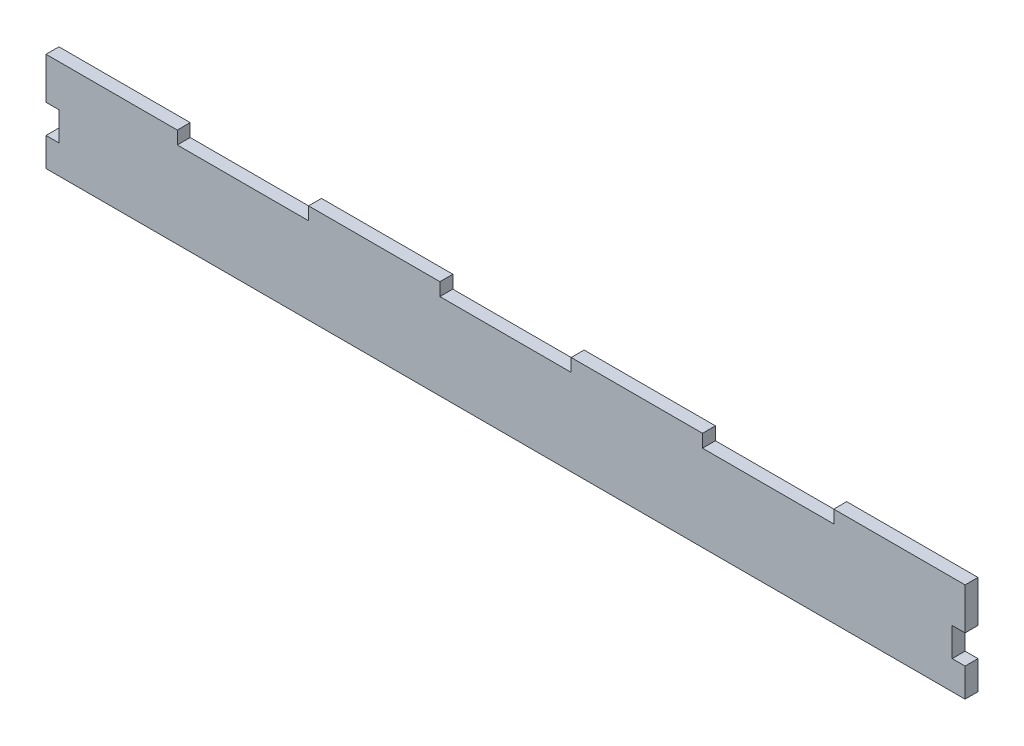
SolidWorks part; units mm, degrees
ref_plane "Front Plane" through (0, 0, 0) normal (0, 0, 1) x (1, 0, 0)
ref_plane "Top Plane" through (0, 0, 0) normal (0, 1, 0) x (1, 0, 0)
ref_plane "Right Plane" through (0, 0, 0) normal (1, 0, 0) x (0, 0, -1)
sketch "Sketch1" plane through (0, 0, 0) normal (0, 1, 0) x (1, 0, 0)
  line L1 (-207.5, -63.25) -> (207.5, -63.25)
  line L2 (-207.5, -63.25) -> (-207.5, 63.25)
  line L3 (-207.5, 63.25) -> (207.5, 63.25)
  line L4 (207.5, -63.25) -> (207.5, 63.25)
  line L5 (-207.5, -63.25) -> (207.5, 63.25) construction
  line L6 (-207.5, 63.25) -> (207.5, -63.25) construction
  point P0 (0, 0)
  dimension "D1" = 126.5
  dimension "D2" = 415
extrude "Boss-Extrude1" add sketch "Sketch1" along normal blind 6
sketch "Sketch2" plane through (0, 6, 0) normal (0, 1, 0) x (1, 0, 0)
  line L0 (213.5, -69.25) -> (213.5, 69.25)
  line L3 (-213.5, -69.25) -> (213.5, -69.25)
  line L4 (207.5, -63.25) -> (207.5, 63.25)
  line L5 (207.5, 63.25) -> (-207.5, 63.25)
  line L6 (-207.5, 63.25) -> (-207.5, -63.25)
  line L7 (-207.5, -63.25) -> (207.5, -63.25)
  line L8 (207.5, -63.25) -> (207.5, 63.25)
  line L9 (207.5, 63.25) -> (-207.5, 63.25)
  line L10 (-207.5, 63.25) -> (-207.5, -63.25)
  line L11 (-207.5, -63.25) -> (207.5, -63.25)
  line L12 (231.5, -87.25) -> (231.5, 87.25)
  line L13 (231.5, 87.25) -> (-231.5, 87.25)
  line L14 (-231.5, 87.25) -> (-231.5, -87.25)
  line L15 (-231.5, -87.25) -> (231.5, -87.25)
  line L16 (237.5, -93.25) -> (237.5, 93.25)
  line L19 (-237.5, -93.25) -> (237.5, -93.25)
  line L20 (213.5, 69.25) -> (-213.5, 69.25) construction
  line L21 (-213.5, 69.25) -> (-213.5, -69.25) construction
  line L22 (-213.5, -69.25) -> (-213.5, -63.25)
  line L27 (152.5, 69.25) -> (91.5, 69.25)
  line L28 (152.5, 69.25) -> (152.5, 63.25)
  line L29 (152.5, 63.25) -> (91.5, 63.25)
  line L30 (91.5, 69.25) -> (91.5, 63.25)
  line L31 (91.5, 69.25) -> (30.5, 69.25)
  line L32 (91.5, 69.25) -> (91.5, 63.25)
  line L33 (91.5, 63.25) -> (30.5, 63.25)
  line L34 (30.5, 69.25) -> (30.5, 63.25)
  line L35 (30.5, 69.25) -> (-30.5, 69.25)
  line L36 (30.5, 69.25) -> (30.5, 63.25)
  line L37 (30.5, 63.25) -> (-30.5, 63.25)
  line L38 (-30.5, 69.25) -> (-30.5, 63.25)
  line L39 (-30.5, 69.25) -> (-91.5, 69.25)
  line L40 (-30.5, 69.25) -> (-30.5, 63.25)
  line L41 (-30.5, 63.25) -> (-91.5, 63.25)
  line L42 (-91.5, 69.25) -> (-91.5, 63.25)
  line L43 (-91.5, 69.25) -> (-152.5, 69.25)
  line L44 (-91.5, 69.25) -> (-91.5, 63.25)
  line L45 (-91.5, 63.25) -> (-152.5, 63.25)
  line L46 (-152.5, 69.25) -> (-152.5, 63.25)
  line L47 (-152.5, 69.25) -> (-213.5, 69.25)
  line L48 (-152.5, 69.25) -> (-152.5, 63.25)
  line L49 (-152.5, 63.25) -> (-213.5, 63.25)
  line L50 (-213.5, 69.25) -> (-213.5, 63.25)
  line L51 (-213.5, 63.25) -> (-207.5, 63.25)
  line L52 (-213.5, 63.25) -> (-213.5, 37.95)
  line L53 (-213.5, 37.95) -> (-207.5, 37.95)
  line L54 (-207.5, 63.25) -> (-207.5, 37.95)
  line L55 (-207.5, 37.95) -> (-213.5, 37.95)
  line L56 (-207.5, 37.95) -> (-207.5, 12.65)
  line L57 (-207.5, 12.65) -> (-213.5, 12.65)
  line L58 (-213.5, 37.95) -> (-213.5, 12.65)
  line L59 (-213.5, 12.65) -> (-207.5, 12.65)
  line L60 (-213.5, 12.65) -> (-213.5, -12.65)
  line L61 (-213.5, -12.65) -> (-207.5, -12.65)
  line L62 (-207.5, 12.65) -> (-207.5, -12.65)
  line L63 (-207.5, -12.65) -> (-213.5, -12.65)
  line L64 (-207.5, -12.65) -> (-207.5, -37.95)
  line L65 (-207.5, -37.95) -> (-213.5, -37.95)
  line L66 (-213.5, -12.65) -> (-213.5, -37.95)
  line L67 (-213.5, -37.95) -> (-207.5, -37.95)
  line L68 (-213.5, -37.95) -> (-213.5, -63.25)
  line L69 (-213.5, -63.25) -> (-207.5, -63.25)
  line L70 (-207.5, -37.95) -> (-207.5, -63.25)
  line L71 (152.5, 63.25) -> (213.5, 63.25)
  line L72 (152.5, 63.25) -> (152.5, 69.25)
  line L73 (152.5, 69.25) -> (213.5, 69.25)
  line L74 (213.5, 63.25) -> (213.5, 69.25)
  line L75 (-237.5, 93.25) -> (-231.5, 93.25)
  line L76 (-237.5, 93.25) -> (-237.5, 55.95)
  line L77 (-237.5, 55.95) -> (-231.5, 55.95)
  line L78 (-231.5, 93.25) -> (-231.5, 55.95)
  line L79 (-237.5, 93.25) -> (-237.5, -93.25) construction
  line L80 (-231.5, 55.95) -> (-237.5, 55.95)
  line L81 (-231.5, 55.95) -> (-231.5, 18.65)
  line L82 (-231.5, 18.65) -> (-237.5, 18.65)
  line L83 (-237.5, 55.95) -> (-237.5, 18.65)
  line L84 (-237.5, 18.65) -> (-231.5, 18.65)
  line L85 (-237.5, 18.65) -> (-237.5, -18.65)
  line L86 (-237.5, -18.65) -> (-231.5, -18.65)
  line L87 (-231.5, 18.65) -> (-231.5, -18.65)
  line L88 (-231.5, -18.65) -> (-237.5, -18.65)
  line L89 (-231.5, -18.65) -> (-231.5, -55.95)
  line L90 (-231.5, -55.95) -> (-237.5, -55.95)
  line L91 (-237.5, -18.65) -> (-237.5, -55.95)
  line L92 (-237.5, -55.95) -> (-231.5, -55.95)
  line L93 (-237.5, -55.95) -> (-237.5, -93.25)
  line L94 (-237.5, -93.25) -> (-231.5, -93.25)
  line L95 (-231.5, -55.95) -> (-231.5, -93.25)
  line L96 (231.5, 87.25) -> (165.3571, 87.25)
  line L97 (231.5, 87.25) -> (231.5, 93.25)
  line L98 (231.5, 93.25) -> (165.3571, 93.25)
  line L99 (165.3571, 87.25) -> (165.3571, 93.25)
  line L100 (165.3571, 93.25) -> (99.2143, 93.25)
  line L101 (165.3571, 93.25) -> (165.3571, 87.25)
  line L102 (165.3571, 87.25) -> (99.2143, 87.25)
  line L103 (99.2143, 93.25) -> (99.2143, 87.25)
  line L104 (99.2143, 87.25) -> (33.0714, 87.25)
  line L105 (99.2143, 87.25) -> (99.2143, 93.25)
  line L106 (99.2143, 93.25) -> (33.0714, 93.25)
  line L107 (33.0714, 87.25) -> (33.0714, 93.25)
  line L108 (33.0714, 93.25) -> (-33.0714, 93.25)
  line L109 (33.0714, 93.25) -> (33.0714, 87.25)
  line L110 (33.0714, 87.25) -> (-33.0714, 87.25)
  line L111 (-33.0714, 93.25) -> (-33.0714, 87.25)
  line L112 (-33.0714, 87.25) -> (-99.2143, 87.25)
  line L113 (-33.0714, 87.25) -> (-33.0714, 93.25)
  line L114 (-33.0714, 93.25) -> (-99.2143, 93.25)
  line L115 (-99.2143, 87.25) -> (-99.2143, 93.25)
  line L116 (-99.2143, 93.25) -> (-165.3571, 93.25)
  line L117 (-99.2143, 93.25) -> (-99.2143, 87.25)
  line L118 (-99.2143, 87.25) -> (-165.3571, 87.25)
  line L119 (-165.3571, 93.25) -> (-165.3571, 87.25)
  line L120 (-165.3571, 87.25) -> (-231.5, 87.25)
  line L121 (-165.3571, 87.25) -> (-165.3571, 93.25)
  line L122 (-165.3571, 93.25) -> (-231.5, 93.25)
  line L123 (-231.5, 87.25) -> (-231.5, 93.25)
  line L124 (237.5, 93.25) -> (-237.5, 93.25) construction
  line L125 (237.5, 93.25) -> (231.5, 93.25)
  line M93 (207.5, 63.25) -> (-207.5, 63.25)
  dimension "D1" = 0
  dimension "D2" = 6
  dimension "D3" = 18
  dimension "D4" = 6
extrude "Boss-Extrude2" add sketch "Sketch2" against normal blind 40 contours L47 L50 L49 L46 M93 | L43 L46 L9 L42 | L39 L42 L38 M93 | L35 L38 L9 L34 | L31 L34 L30 M93 | L27 L30 L9 L28 | L73 L28 L71 L0 M93 region at (183, 6, -66.25) region at (122, 6, -66.25) region at (61, 6, -66.25) region at (0, 6, -66.25) region at (-61, 6, -66.25) region at (-122, 6, -66.25) region at (-183, 6, -66.25)
extrude "Cut-Extrude1" cut sketch "Sketch1<2>" against normal through all both and the other way through all
sketch "Sketch1<2>" plane through (0, 0, 0) normal (0, 1, 0) x (1, 0, 0) same geometry as "Sketch1"
extrude "Boss-Extrude3" add sketch "Sketch2<4>" along normal blind 6 contours L47 L50 L49 L46 M93 | L39 L42 L38 M93 | L31 L34 L30 M93 | L73 L28 L71 L0 M93 region at (183, 6, -66.25) region at (61, 6, -66.25) region at (-61, 6, -66.25) region at (-183, 6, -66.25)
sketch "Sketch2<4>" plane through (0, 6, 0) normal (0, 1, 0) x (1, 0, 0) same geometry as "Sketch2"
sketch "Sketch3" plane through (0, 0, -63.25) normal (0, 0, 1) x (1, 0, 0)
  line L0 (-213.5, -34) -> (-213.5, 12) construction
  line L1 (-213.5, -34) -> (-207.5, -34)
  line L2 (-213.5, -34) -> (-213.5, -20.6667)
  line L3 (-213.5, -20.6667) -> (-207.5, -20.6667)
  line L4 (-207.5, -34) -> (-207.5, -20.6667)
  line L5 (-207.5, -20.6667) -> (-213.5, -20.6667)
  line L6 (-207.5, -20.6667) -> (-207.5, -7.3333)
  line L7 (-207.5, -7.3333) -> (-213.5, -7.3333)
  line L8 (-213.5, -20.6667) -> (-213.5, -7.3333)
  line L10 (-213.5, -7.3333) -> (-207.5, -7.3333)
  line L11 (-213.5, -7.3333) -> (-213.5, 6)
  line L12 (-213.5, 6) -> (-207.5, 6)
  line L13 (-207.5, -7.3333) -> (-207.5, 6)
  line L14 (-207.5, 6) -> (-213.5, 6) construction
  point P11 (-207.5, 6)
  line M8 (-213.5, 12) -> (-213.5, -34)
  dimension "D1" = 6
extrude "Cut-Extrude2" cut sketch "Sketch3" against normal blind 6 contours L6 L7 L3 M8 region at (-210.5, -14, -63.25)
mirror "Mirror1" about plane through (0, 0, 0) normal (1, 0, 0) of "Cut-Extrude2"
